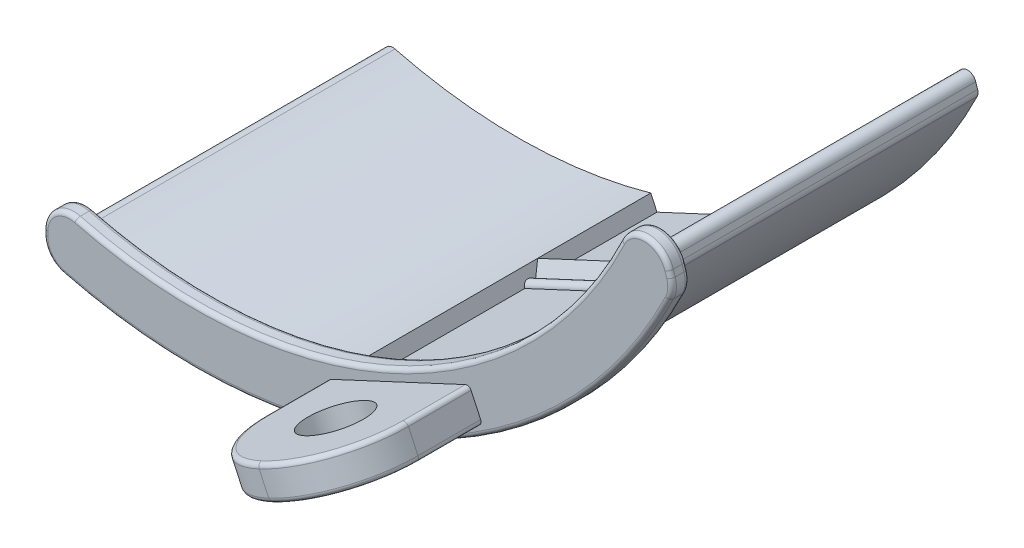
SolidWorks part; units mm, degrees
ref_plane "Plane1" through (0, 0, 0) normal (0, 0, 1) x (1, 0, 0)
ref_plane "Plane2" through (0, 0, 0) normal (0, 1, 0) x (1, 0, 0)
ref_plane "Plane3" through (0, 0, 0) normal (1, 0, 0) x (0, 0, -1)
sketch "Sketch1" plane through (0, 0, 0) normal (0, 0, 1) x (1, 0, 0)
  line L2 (54.8411, -24.5761) -> (54.6285, -23.9146)
  line L3 (-17.28, -55.616) -> (-17.28, -56.1114)
  line L4 (54.8411, -24.5761) -> (54.6285, -23.9146)
  line L5 (-17.28, -55.616) -> (-17.28, -56.1114)
  arc A6 (-17.28, -56.1114) -> (-15.0199, -59.0187) centre (-14.28, -56.1114) ccw
  arc A7 (-15.0199, -59.0187) -> (54.6786, -26.8152) centre (0, 0) ccw
  arc A8 (54.6786, -26.8152) -> (54.8411, -24.5761) centre (51.9851, -25.4943) ccw
  arc A9 (54.6285, -23.9146) -> (49.0675, -23.5354) centre (51.7725, -24.8328) ccw
  arc A10 (-13.5339, -52.7102) -> (49.0675, -23.5354) centre (0, 0) ccw
  arc A11 (-13.5339, -52.7102) -> (-17.28, -55.616) centre (-14.28, -55.616) ccw
  arc A12 (-17.28, -56.1114) -> (-15.0199, -59.0187) centre (-14.28, -56.1114) ccw
  arc A13 (-15.0199, -59.0187) -> (54.6786, -26.8152) centre (0, 0) ccw
  arc A14 (54.6786, -26.8152) -> (54.8411, -24.5761) centre (51.9851, -25.4943) ccw
  arc A15 (54.6285, -23.9146) -> (49.0675, -23.5354) centre (51.7725, -24.8328) ccw
  arc A16 (-13.5339, -52.7102) -> (49.0675, -23.5354) centre (0, 0) ccw
  arc A17 (-13.5339, -52.7102) -> (-17.28, -55.616) centre (-14.28, -55.616) ccw
  dimension "D1" = 0
extrude "Base-Extrude" add sketch "Sketch1" along normal blind 2
sketch "Sketch2" plane through (0, 0, 2) normal (0, 0, 1) x (1, 0, 0)
  line L0 (-15.28, -55.616) -> (-15.28, -56.1114) construction
  line L1 (-15.28, -55.616) -> (-15.28, -56.1114)
  line L2 (52.9371, -25.1882) -> (52.7245, -24.5268) construction
  line L3 (52.9371, -25.1882) -> (52.7245, -24.5268)
  arc A0 (-14.0313, -54.6474) -> (50.8708, -24.4004) centre (0, 0) ccw construction
  arc A1 (-14.0313, -54.6474) -> (50.8708, -24.4004) centre (0, 0) ccw
  arc A2 (-14.5266, -57.0805) -> (52.883, -25.9346) centre (0, 0) ccw construction
  arc A3 (-14.5266, -57.0805) -> (52.883, -25.9346) centre (0, 0) ccw
  arc A4 (52.7245, -24.5268) -> (50.8708, -24.4004) centre (51.7725, -24.8328) ccw construction
  arc A5 (52.7245, -24.5268) -> (50.8708, -24.4004) centre (51.7725, -24.8328) ccw
  arc A6 (-14.0313, -54.6474) -> (-15.28, -55.616) centre (-14.28, -55.616) ccw construction
  arc A7 (-14.0313, -54.6474) -> (-15.28, -55.616) centre (-14.28, -55.616) ccw
  arc A8 (-15.28, -56.1114) -> (-14.5266, -57.0805) centre (-14.28, -56.1114) ccw construction
  arc A9 (-15.28, -56.1114) -> (-14.5266, -57.0805) centre (-14.28, -56.1114) ccw
  arc A10 (52.883, -25.9346) -> (52.9371, -25.1882) centre (51.9851, -25.4943) ccw construction
  arc A11 (52.883, -25.9346) -> (52.9371, -25.1882) centre (51.9851, -25.4943) ccw
extrude "Boss-Extrude1" add sketch "Sketch2" against normal blind 37.16
sketch "Sketch3" plane through (0, 0, 2) normal (0, 0, 1) x (1, 0, 0)
  line L0 (-14.28, -55.616) -> (51.7725, -24.8328) construction
  line L1 (10.2535, -22.0012) -> (18.7462, -40.2244) construction
  line L3 (31.6672, -46.6436) -> (33.1879, -49.9066)
  line L4 (33.1879, -49.9066) -> (16.8727, -57.5102)
  line L5 (16.8727, -57.5102) -> (15.352, -54.2471)
  line L6 (15.352, -54.2471) -> (31.6672, -46.6436)
  dimension "D1" = 18
  dimension "D2" = 3.6
extrude "Boss-Extrude2" add sketch "Sketch3" along normal blind 16.2
fillet "Fillet1" radius 9 2 edges at (16.1123, -55.8786, 18.2) (32.4276, -48.2751, 18.2)
sketch "Sketch4" plane through (25.0303, -53.7084, 0) normal (0.4224, -0.9064, 0) x (0.9064, 0.4224, 0)
  circle A0 centre (0, 9.2) radius 3.52
  arc A1 (0, 18.2) -> (-9, 9.2) centre (0, 9.2) ccw construction
  dimension "D1" = 7.04
extrude "Cut-Extrude1" cut sketch "Sketch4" against normal through all
fillet "Fillet3" radius 0.5 24 edges at (22.9881, -49.3263, 2) (22.9881, -49.3263, 0) (-16.1187, -53.2455, 2) (51.9766, -21.8398, 2) (-16.1187, -53.2455, 0) (51.9766, -21.8398, 0) (33.1879, -49.9066, 5.6) (31.6672, -46.6436, 5.6) (-17.28, -55.8637, 2) (54.7348, -24.2453, 2) (-17.28, -55.8637, 0) (54.7348, -24.2453, 0) (30.7986, -51.0201, 15.564) (29.2779, -47.7571, 15.564) (-16.6485, -57.9527, 2) (54.9772, -25.7114, 2) (-16.6485, -57.9527, 0) (54.9772, -25.7114, 0) (19.262, -56.3966, 15.564) (17.7413, -53.1336, 15.564) (25.5435, -55.2842, 2) (25.5435, -55.2842, 0) (16.8727, -57.5102, 5.6) (15.352, -54.2471, 5.6)
sketch "Sketch6" plane through (0, 0, -35.16) normal (0, 0, -1) x (-1, 0, 0)
  line L1 (-32.4045, -48.2256) -> (-16.0893, -55.8292)
  line L2 (-31.8784, -47.0968) -> (-32.9767, -49.4534) construction
  line L3 (-16.6615, -57.057) -> (-15.5632, -54.7003) construction
  line L4 (-15.8052, -54.0359) -> (-31.214, -46.8548) construction
  line L5 (-32.4045, -48.2256) -> (-31.6853, -46.6825)
  line L6 (-16.0893, -55.8292) -> (-15.3701, -54.2861)
  arc A0 (-52.883, -25.9346) -> (14.5266, -57.0805) centre (0, 0) ccw construction
  arc A1 (-50.8708, -24.4004) -> (14.0313, -54.6474) centre (0, 0) ccw construction
  arc A2 (-31.6853, -46.6825) -> (-15.3701, -54.2861) centre (0, 0) ccw
  dimension "D1" = 1.5
extrude "Cut-Extrude3" cut sketch "Sketch6" against normal up to surface (35.16 mm away) up to face at (20.0459, -43.0215, 0)
sketch "Sketch7" plane through (8.1576, 3.8018, 0) normal (-0.9064, -0.4224, 0) x (0, 0, 1)
  line L0 (-25.66, -57.4) -> (-22.16, -55.6975)
  line L1 (0, -57.4) -> (-35.16, -57.4) construction
  line L2 (-22.16, -55.6975) -> (-21.16, -57.4)
  line L3 (-35.16, -57.4) -> (-35.16, -55.6975) construction
  line L4 (-35.16, -45.6015) -> (-35.16, -58.9) construction
  line L5 (-19.96, -57.4) -> (-21.16, -57.5667)
  line L6 (-21.16, -57.5667) -> (-25.66, -57.4)
  arc A0 (-21.16, -57.4) -> (-19.96, -57.4) centre (-20.56, -57.4) cw
  dimension "D4" = 0.6
  dimension "D1" = 9.5
  dimension "D2" = 13
  dimension "D3" = 14
extrude "Boss-Extrude3" add sketch "Sketch7" along normal up to surface (18 mm away) up to face at (15.7297, -55.0576, -17.58)
